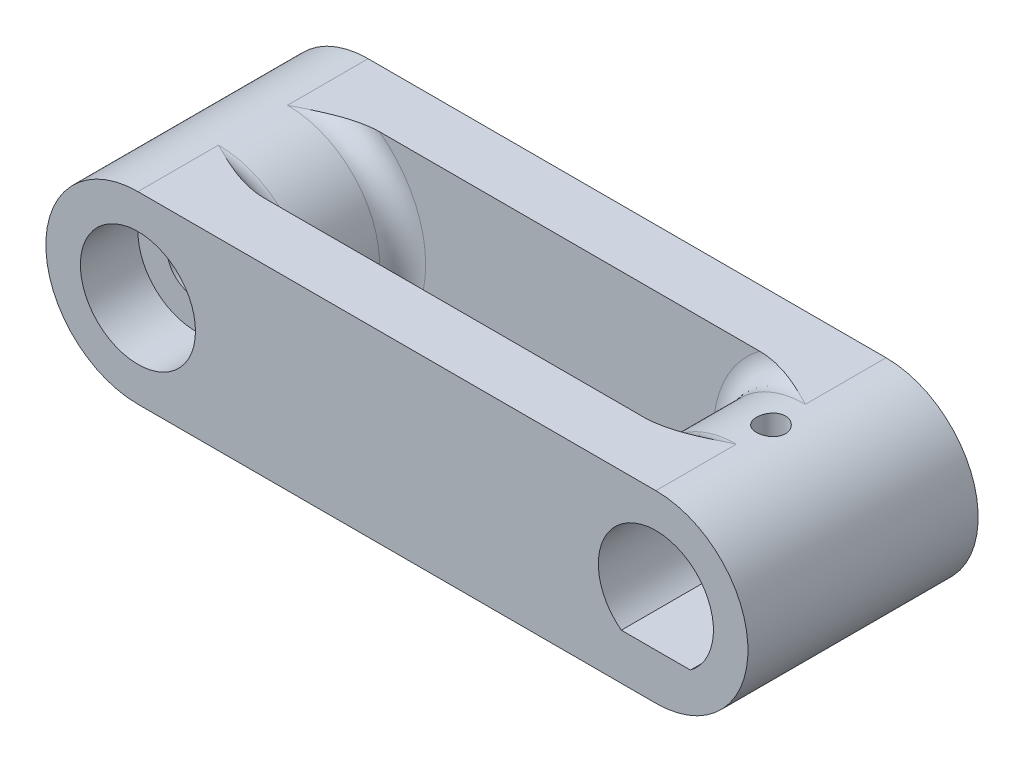
SolidWorks part; units mm, degrees
ref_plane "前视基准面" through (0, 0, 0) normal (0, 0, 1) x (1, 0, 0)
ref_plane "上视基准面" through (0, 0, 0) normal (0, 1, 0) x (1, 0, 0)
ref_plane "右视基准面" through (0, 0, 0) normal (1, 0, 0) x (0, 0, -1)
sketch "草图1" plane through (0, 0, 0) normal (0, 0, 1) x (1, 0, 0)
  circle A0 centre (0, 0) radius 8
  dimension "D1" = 16
extrude "凸台-拉伸1" add sketch "草图1" along normal blind 20
sketch "草图2" plane through (0, 0, 20) normal (0, 0, 1) x (1, 0, 0)
  line L0 (-3, -4) -> (3, -4)
  arc A0 (3, -4) -> (-3, -4) centre (0, 0) ccw
  dimension "D1" = 10
  dimension "D2" = 4
extrude "切除-拉伸1" cut sketch "草图2" against normal through all
sketch "草图3" plane through (0, -4, 0) normal (0, 1, 0) x (1, 0, 0)
  line L0 (0, -20) -> (0, 0) construction
  line L1 (-8, -20) -> (8, -20) construction
  circle A0 centre (0, -10) radius 1.25
  dimension "D2" = 2.5
  dimension "D1" = 10
extrude "切除-拉伸2" cut sketch "草图3" against normal through all both and the other way through all
sketch "草图4" plane through (0, 0, 0) normal (0, 0, -1) x (-1, 0, 0)
  line L0 (0, -8) -> (45, -8)
  line L1 (0, 8) -> (45, 8)
  circle A0 centre (0, 0) radius 8 construction
  arc A1 (45, -8) -> (45, 8) centre (45, 0) ccw
  arc A2 (0, -8) -> (0, 8) centre (0, 0) ccw
  dimension "D1" = 45
  dimension "D2" = 16
extrude "凸台-拉伸2" add sketch "草图4" against normal blind 5
sketch "草图5" plane through (0, 0, 20) normal (0, 0, 1) x (1, 0, 0)
  line L0 (0, 8) -> (-45, 8)
  line L1 (0, -8) -> (-45, -8)
  circle A0 centre (0, 0) radius 8 construction
  arc A1 (-45, 8) -> (-45, -8) centre (-45, 0) ccw
  arc A2 (0, 8) -> (0, -8) centre (0, 0) ccw
extrude "凸台-拉伸3" add sketch "草图5" against normal blind 5
sketch "草图6" plane through (0, 0, 15) normal (0, 0, -1) x (-1, 0, 0)
  circle A0 centre (45, 0) radius 8
extrude "凸台-拉伸4" add sketch "草图6" along normal blind 10
sketch "草图7" plane through (0, 0, 0) normal (0, 0, -1) x (-1, 0, 0)
  circle A0 centre (45, 0) radius 2.5
  dimension "D1" = 5
extrude "切除-拉伸3" cut sketch "草图7" against normal through all and the other way through all
fillet "圆角1" radius 2 4 edges at (-37, 0, 15) (-37, 0, 5) (-8, 0, 15) (-8, 0, 5)
sketch "草图8" plane through (0, 0, 20) normal (0, 0, 1) x (1, 0, 0)
  circle A0 centre (-45, 0) radius 5
  dimension "D1" = 10
extrude "切除-拉伸4" cut sketch "草图8" against normal blind 5
